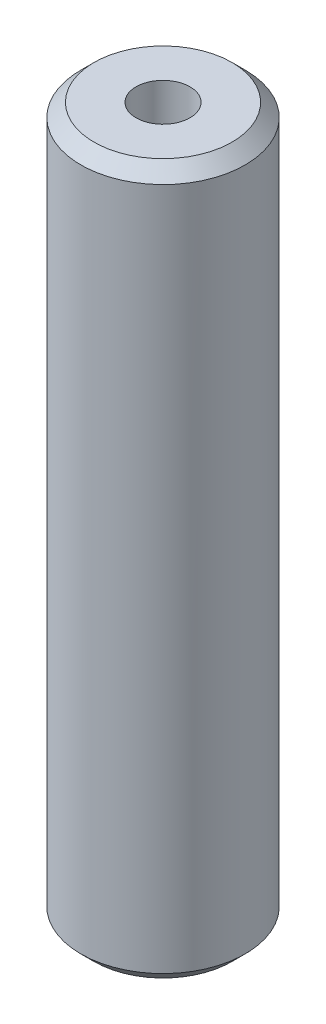
SolidWorks part; units mm, degrees
ref_plane "Front Plane" through (0, 0, 0) normal (0, 0, 1) x (1, 0, 0)
ref_plane "Top Plane" through (0, 0, 0) normal (0, 1, 0) x (1, 0, 0)
ref_plane "Right Plane" through (0, 0, 0) normal (1, 0, 0) x (0, 0, -1)
sketch "Sketch1" plane through (0, 0, 0) normal (0, 1, 0) x (1, 0, 0)
  circle A0 centre (0, 0) radius 10
  dimension "SHAFT_OD" = 20
extrude "Boss-Extrude1" add sketch "Sketch1" along normal blind 86.3352
sketch "Sketch2" plane through (0, 0, 0) normal (0, 1, 0) x (1, 0, 0)
  circle A0 centre (0, 0) radius 3.2756
  dimension "BORE_D" = 6.5511
extrude "Cut-Extrude1" cut sketch "Sketch2" along normal through all
chamfer "Chamfer1" distance 1.6012 angle 45 2 edges at (0, 86.3352, 10) (0, 0, 10)
